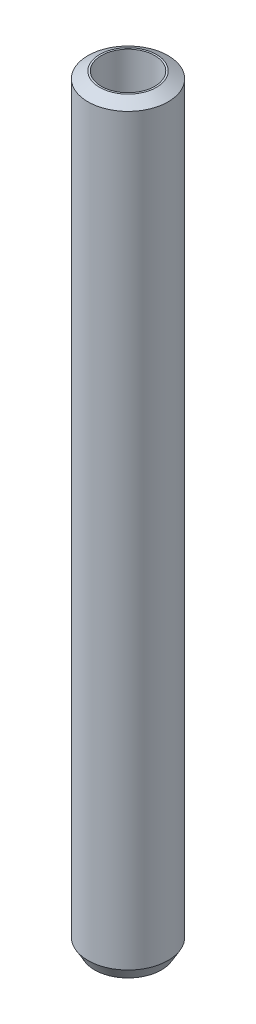
SolidWorks part; units mm, degrees
ref_plane "Front Plane" through (0, 0, 0) normal (0, 0, 1) x (1, 0, 0)
ref_plane "Top Plane" through (0, 0, 0) normal (0, 1, 0) x (1, 0, 0)
ref_plane "Right Plane" through (0, 0, 0) normal (1, 0, 0) x (0, 0, -1)
sketch "Sketch1" plane through (0, 0, 0) normal (0, 1, 0) x (1, 0, 0)
  circle A0 centre (0, 0) radius 12.5
  dimension "SHAFT_OD" = 25
extrude "Boss-Extrude1" add sketch "Sketch1" along normal blind 237.6048
sketch "Sketch2" plane through (0, 0, 0) normal (0, 1, 0) x (1, 0, 0)
  circle A0 centre (0, 0) radius 8.3295
  dimension "BORE_D" = 16.6589
extrude "Cut-Extrude1" cut sketch "Sketch2" along normal through all
chamfer "Chamfer1" distance 2.0948 angle 60 2 edges at (0, 237.6048, 12.5) (0, 0, 12.5) first distance on face at (0, 237.6048, 12.5) first distance on face at (0, 0, 8.3295)
